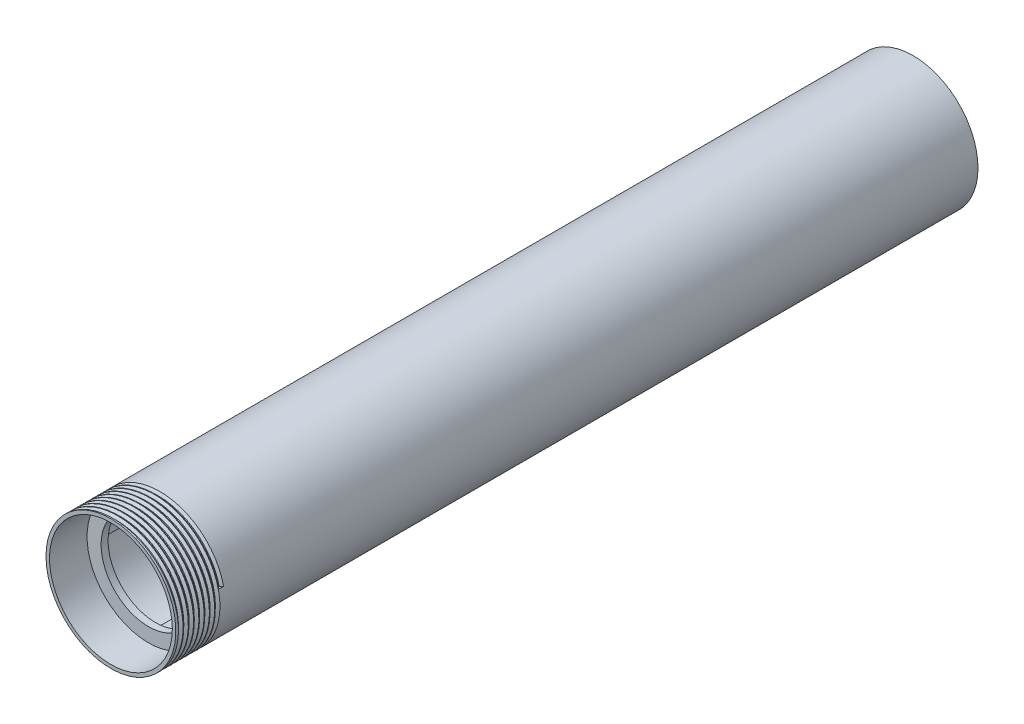
SolidWorks part; units mm, degrees
ref_plane "Front Plane" through (0, 0, 0) normal (0, 0, 1) x (1, 0, 0)
ref_plane "Top Plane" through (0, 0, 0) normal (0, 1, 0) x (1, 0, 0)
ref_plane "Right Plane" through (0, 0, 0) normal (1, 0, 0) x (0, 0, -1)
sketch "Sketch3" plane through (0, 0, 0) normal (0, 0, 1) x (1, 0, 0)
  circle A0 centre (0, 0) radius 18.5
  dimension "D1" = 37
extrude "Extrude-Thin1" add sketch "Sketch3" along normal blind 228.6 thin thin type one direction reverse wall 1
sketch "Sketch4" plane through (0, 0, 0) normal (0, 0, -1) x (-1, 0, 0)
  line L0 (-19.1706, 0) -> (20.7373, 0) construction
  line L1 (0, -20.2013) -> (0, 21.2732) construction
  line L2 (-17.5, 1.524) -> (-16.484, 1.524)
  line L3 (-1.524, -17.5) -> (1.524, -17.5)
  line L4 (-1.524, -17.5) -> (-1.524, -16.484)
  line L5 (-1.524, -16.484) -> (1.524, -16.484)
  line L6 (1.524, -17.5) -> (1.524, -16.484)
  line L7 (-17.5, 1.524) -> (-17.5, -1.524)
  line L8 (-17.5, -1.524) -> (-16.484, -1.524)
  line L9 (-16.484, 1.524) -> (-16.484, -1.524)
  line L10 (1.524, 17.5) -> (1.524, 16.484)
  line L11 (1.524, 17.5) -> (-1.524, 17.5)
  line L12 (-1.524, 17.5) -> (-1.524, 16.484)
  line L13 (1.524, 16.484) -> (-1.524, 16.484)
  line L14 (17.5, -1.524) -> (16.484, -1.524)
  line L15 (17.5, -1.524) -> (17.5, 1.524)
  line L16 (17.5, 1.524) -> (16.484, 1.524)
  line L17 (16.484, -1.524) -> (16.484, 1.524)
  circle A17 centre (0, 0) radius 17.5 construction
  point P18 (1.5875, -1.5875)
  point P19 (0, 0)
  point P25 (0, 0)
  point P29 (0, 0)
  dimension "D1" = 1.016
  dimension "D3" = 1.524
  dimension "D4" = 4
  dimension "D2" = 3.048
extrude "Boss-Extrude1" add sketch "Sketch4" against normal blind 215.9 separate body
sketch "Sketch5" plane through (0, 0, 228.6) normal (0, 0, 1) x (1, 0, 0)
  circle A0 centre (0, 0) radius 18.05
  circle A1 centre (0, 0) radius 13.5
  dimension "D1" = 27
extrude "Boss-Extrude2" add sketch "Sketch5" against normal blind 2 from offset 10.7036 offset against normal yes
thread "Thread1" pitch 1.5 method cut profile "Thread Profile1" start angle 0, offset 0, length 12.7, pitch 1.5, diameter 37
ref_plane "Plane1" through (-18.5, 0, 228.6) normal (0, -1, 0) x (-1, 0, 0)
sketch "Thread Profile1" plane through (-18.5, 0, 228.6) normal (0, -1, 0) x (-1, 0, 0)
  line L0 (0, 0) -> (0, 1.5) construction
  line L11 (0, 0) -> (0, 1.3125)
  line L12 (0, 1.3125) -> (-0.8119, 0.8437)
  line L13 (-0.8119, 0.8437) -> (-0.8119, 0.4687)
  line L15 (-0.8119, 0.4687) -> (0, 0)
  line L17 (-0.8119, 0.6562) -> (0, 0.6562) construction
  point P2 (0, 0)
  dimension "Pitch" = 1.5
  dimension "Profile_Angle" = 60
  dimension "Profile_Land" = 0.375
  dimension "Profile_Height" = 0.8119
